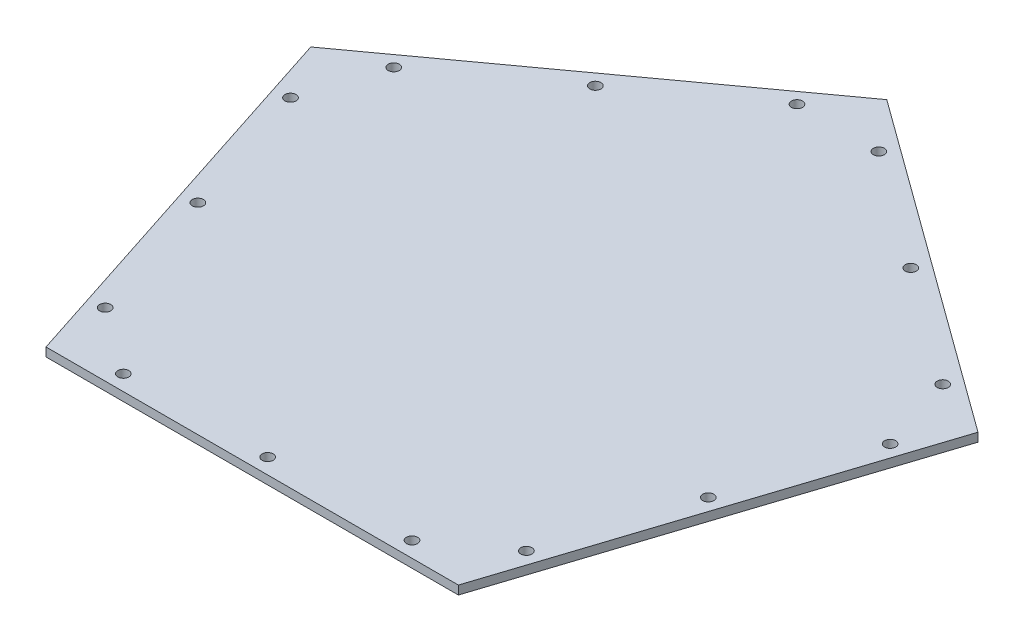
SolidWorks part; units mm, degrees
material "Acrylic (Medium-high impact)"
ref_plane "Front Plane" through (0, 0, 0) normal (0, 0, 1) x (1, 0, 0)
ref_plane "Top Plane" through (0, 0, 0) normal (0, 1, 0) x (1, 0, 0)
ref_plane "Right Plane" through (0, 0, 0) normal (1, 0, 0) x (0, 0, -1)
ref_axis "Axis1" through (0, 36.359, 0) along (0, -1, 0)
sketch "Sketch1" plane through (0, 0, 0) normal (0, 1, 0) x (1, 0, 0)
  line L0 (0, 0) -> (-63.5, -87.4003)
  line L1 (-63.5, -87.4003) -> (0, -87.4003)
  line L2 (0, -87.4003) -> (0, 0) construction
  line L3 (0, 0) -> (63.5, -87.4003)
  line L4 (63.5, -87.4003) -> (0, -87.4003)
  dimension "D1" = 72
  dimension "D2" = 127
extrude "Boss-Extrude1" add sketch "Sketch1" along normal mid plane 2.667
sketch "Sketch2" plane through (0, -1.3335, 0) normal (0, -1, 0) x (1, 0, 0)
  line L0 (-44.45, 82.6378) -> (44.45, 82.6378) construction
  line L1 (-63.5, 87.4003) -> (63.5, 87.4003) construction
  circle A0 centre (-44.45, 82.6378) radius 1.7145
  circle A1 centre (0, 82.6378) radius 1.7145
  circle A2 centre (44.45, 82.6378) radius 1.7145
  point P9 (0, 82.6378)
  dimension "D2" = 3.429
  dimension "D1" = 19.05
  dimension "D3" = 4.7625
extrude "Cut-Extrude1" cut sketch "Sketch2" against normal through all both and the other way through all
pattern_circular "CirPattern1" count 5 over 360 about axis through (0, 1.3335, 0) along (0, -1, 0) of "Boss-Extrude1", "Cut-Extrude1" reverse direction yes
equation "\"sides\"= 5"
equation "\"edge\"= 5in"
equation "\"D1@Sketch1\"=360/\"sides\""
equation "\"D2@Sketch1\"=\"edge\""
equation "\"D1@CirPattern1\"=\"sides\""
